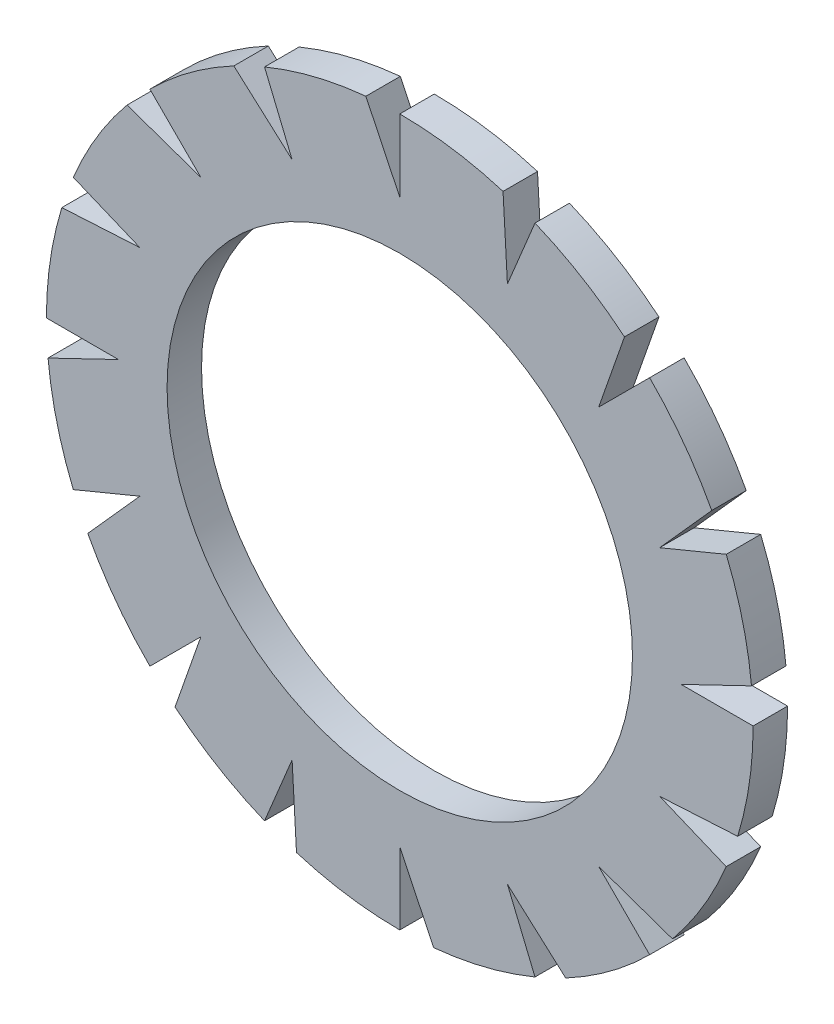
SolidWorks part; units mm, degrees
ref_plane "Front Plane" through (0, 0, 0) normal (0, 0, 1) x (1, 0, 0)
ref_plane "Top Plane" through (0, 0, 0) normal (0, 1, 0) x (1, 0, 0)
ref_plane "Right Plane" through (0, 0, 0) normal (1, 0, 0) x (0, 0, -1)
sketch "BodySke" plane through (0, 0, 0) normal (0, 1, 0) x (1, 0, 0)
  line L0 (0, 0) -> (0, 16) construction
  line L2 (6.75, 0) -> (10.25, 0)
  line L3 (6.75, 0) -> (6.75, 1)
  line L4 (6.75, 1) -> (10.25, 1)
  line L5 (10.25, 0) -> (10.25, 1)
revolve "BaseBody" add sketch "BodySke" angle 360 about L0
sketch "ToothSke" plane through (0, 0, 0) normal (0, 0, 1) x (1, 0, 0)
  line L0 (0, 0) -> (0, 2.7341) construction
  line L1 (0, 8.16) -> (0, 10.25)
  line L2 (-0.7966, 8.121) -> (-1.0063, 10.25) construction
  line L3 (1.0063, 10.25) -> (-1.0063, 10.25) construction
  line L4 (0.7966, 8.121) -> (1.0063, 10.25) construction
  line L5 (0, 8.16) -> (-1.0063, 10.25)
  line L6 (-1.0063, 10.25) -> (0, 10.25)
  circle A0 centre (0, 0) radius 8.16 construction
  arc A1 (-0.7966, 8.121) -> (0.7966, 8.121) centre (0, 0) cw construction
  circle A2 centre (0, 0) radius 6.75 construction
  circle A3 centre (0, 0) radius 6.75 construction
  circle A4 centre (0, 0) radius 10.25 construction
  point P11 (0, 1.083)
  point P12 (0, 8.16)
  point P15 (0, 2.4103)
  point P16 (0, 10.25)
  dimension "D1" = 16.32
  dimension "D2" = 2.0126
  dimension "D3" = 11.25
extrude "ToothCut" cut sketch "ToothSke" against normal through all
pattern_circular "ToothPat" count 16 over 360 about axis through (0, 0, 0) along (0, 0, -1) of "ToothCut"
equation "\"D1@ToothSke\" =  ( \"Inner_dia@BodySke\" + \"Outer_dia@BodySke\" )  * 0.48"
equation "\"D2@ToothSke\" =  pi  * \"Outer_dia@BodySke\" / 2 / \"Num_tooth@BodySke\""
equation "\"D3@ToothSke\" = 360 / 2 / \"Num_tooth@BodySke\" "
equation "\"Num_tooth@ToothPat\" = \"Num_tooth@BodySke\""
